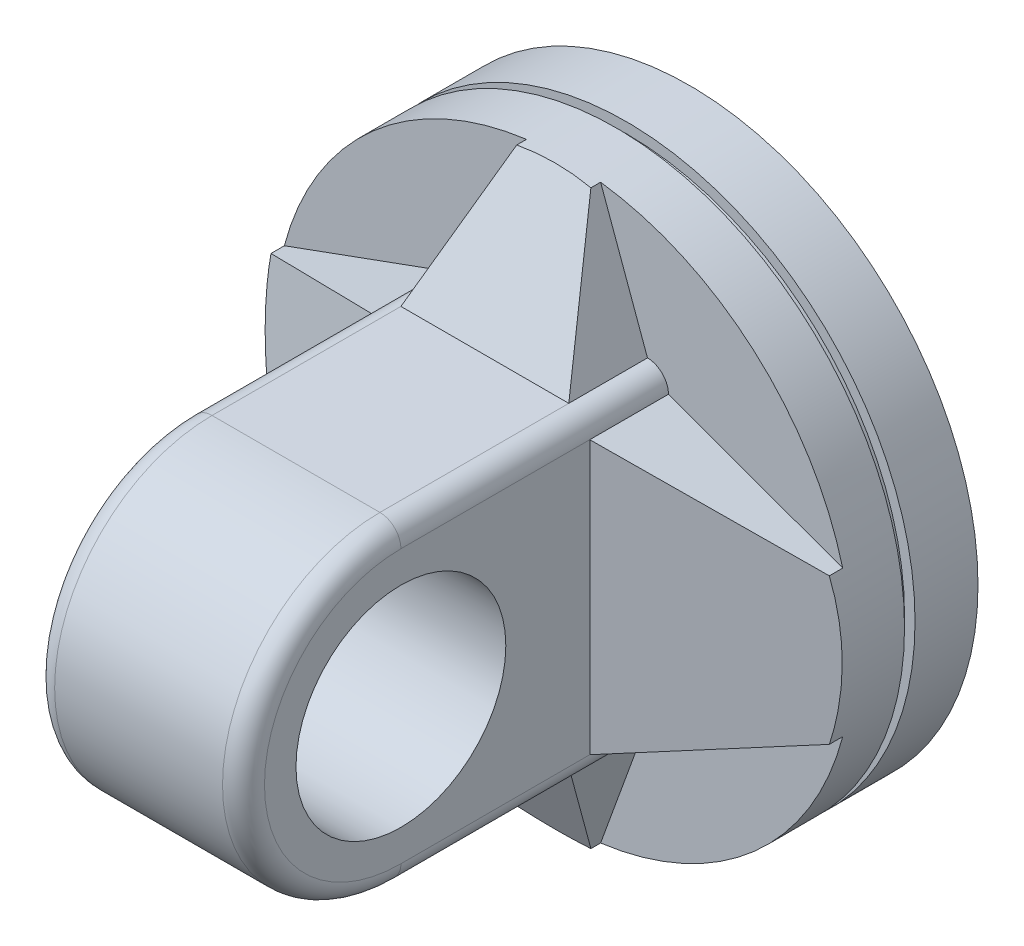
SolidWorks part; units mm, degrees
ref_plane "Front Plane" through (0, 0, 0) normal (0, 0, 1) x (1, 0, 0)
ref_plane "Top Plane" through (0, 0, 0) normal (0, 1, 0) x (1, 0, 0)
ref_plane "Right Plane" through (0, 0, 0) normal (1, 0, 0) x (0, 0, -1)
sketch "Sketch1" plane through (0, 0, 0) normal (0, 0, 1) x (1, 0, 0)
  circle A0 centre (0, 0) radius 275
  dimension "D1" = 550
extrude "Boss-Extrude1" add sketch "Sketch1" along normal blind 70
sketch "Sketch2" plane through (0, 0, 70) normal (0, 0, 1) x (1, 0, 0)
  circle A0 centre (0, 0) radius 275 construction
  circle A1 centre (0, 0) radius 275
  circle A2 centre (0, 0) radius 265
  dimension "D1" = 10
extrude "Cut-Extrude1" cut sketch "Sketch2" against normal blind 10
sketch "Sketch3" plane through (0, 0, 70) normal (0, 0, 1) x (1, 0, 0)
  circle A0 centre (0, 0) radius 275 construction
  circle A1 centre (0, 0) radius 275
extrude "Boss-Extrude2" add sketch "Sketch3" along normal blind 50
sketch "Sketch4" plane through (0, 0, 0) normal (1, 0, 0) x (0, 0, -1)
  circle A0 centre (-375, 0) radius 100
  circle A1 centre (-375, 0) radius 150
  dimension "D1" = 200
  dimension "D2" = 375
  dimension "D3" = 300
extrude "Boss-Extrude3" add sketch "Sketch4" along normal mid plane 200 separate body contours A0 A1 | A1 | A1 region at (0, 0, 520.7574)
sketch "Sketch6" plane through (0, 0, 0) normal (1, 0, 0) x (0, 0, -1)
  line L0 (-375, 150) -> (-120, 150)
  line L1 (-120, 275) -> (-120, -275) construction
  line L2 (-375, -150) -> (-120, -150)
  line L3 (-120, -150) -> (-120, 150)
  circle A0 centre (-375, 0) radius 150 construction
  arc A1 (-375, -150) -> (-375, 150) centre (-375, 0) ccw
extrude "Boss-Extrude4" add sketch "Sketch6" along normal mid plane 200
fillet "Fillet3" radius 20 6 edges at (100, 150, 247.5) (100, -150, 247.5) (-100, 150, 247.5) (-100, -150, 247.5) (100, 0, 525) (-100, 0, 525)
sketch "Sketch7" plane through (0, 0, 120) normal (0, 0, 1) x (1, 0, 0)
  line L0 (-80, -150) -> (-35.3333, -272.7207)
  line L1 (80, -150) -> (-80, -150) construction
  line L2 (0, -1000) -> (0, 49000) construction
  line L3 (-1000, 0) -> (49000, 0) construction
  line L4 (100, -130) -> (266.0571, -69.5602)
  line L5 (100, -130) -> (100, 130) construction
  line L6 (80, -150) -> (35.3333, -272.7207)
  line L7 (100, 130) -> (266.0571, 69.5602)
  line L8 (-100, -130) -> (-266.0571, -69.5602)
  line L9 (-100, 130) -> (-266.0571, 69.5602)
  line L10 (80, 150) -> (35.3333, 272.7207)
  line L11 (-80, 150) -> (-35.3333, 272.7207)
  arc A0 (-100, -130) -> (-80, -150) centre (-80, -130) ccw construction
  circle A1 centre (0, 0) radius 275
  circle A2 centre (0, 0) radius 275
  circle M8 centre (0, 0) radius 275
  line M9 (100, 130) -> (100, -130)
  line M11 (80, -150) -> (-80, -150)
  line M13 (-100, -130) -> (-100, 130)
  line M15 (-80, 150) -> (80, 150)
  dimension "D2" = 70
  dimension "D3" = 70
  dimension "D1" = 0
extrude "Boss-Extrude5" add sketch "Sketch7" along normal blind 75 contours L9 L8 M13 M8 | L7 L4 M9 M8 | L11 L10 M15 M8 | L6 L0 M11 M8 region at (0, -203.968, 120) region at (-176.9734, 0, 120) region at (176.9734, 0, 120) region at (0, 203.968, 120)
sketch "Sketch8" plane through (0, 0, 0) normal (0, 1, 0) x (1, 0, 0)
  line L4 (-300, -120) -> (-100, -195)
  line L5 (0, -1000) -> (0, 49000) construction
  line L7 (300, -120) -> (100, -195)
  line L9 (-100, -195) -> (-300, -195)
  line L10 (-300, -195) -> (-300, -120)
  line L11 (300, -120) -> (300, -195)
  line L12 (300, -195) -> (100, -195)
  dimension "D1" = 200
  dimension "D2" = 75
extrude "Cut-Extrude4" cut sketch "Sketch8" against normal mid plane 300
sketch "Sketch9" plane through (0, 0, 0) normal (1, 0, 0) x (0, 0, -1)
  line L0 (-195, 150) -> (-195, 290)
  line L1 (-195, 290) -> (-120, 290)
  line L2 (-120, 290) -> (-195, 150)
  line L3 (-1000, 0) -> (49000, 0) construction
  line L4 (-120, -290) -> (-195, -150)
  line L5 (-195, -150) -> (-195, -290)
  line L6 (-195, -290) -> (-120, -290)
  dimension "D1" = 75
  dimension "D2" = 140
extrude "Cut-Extrude5" cut sketch "Sketch9" against normal mid plane 175
